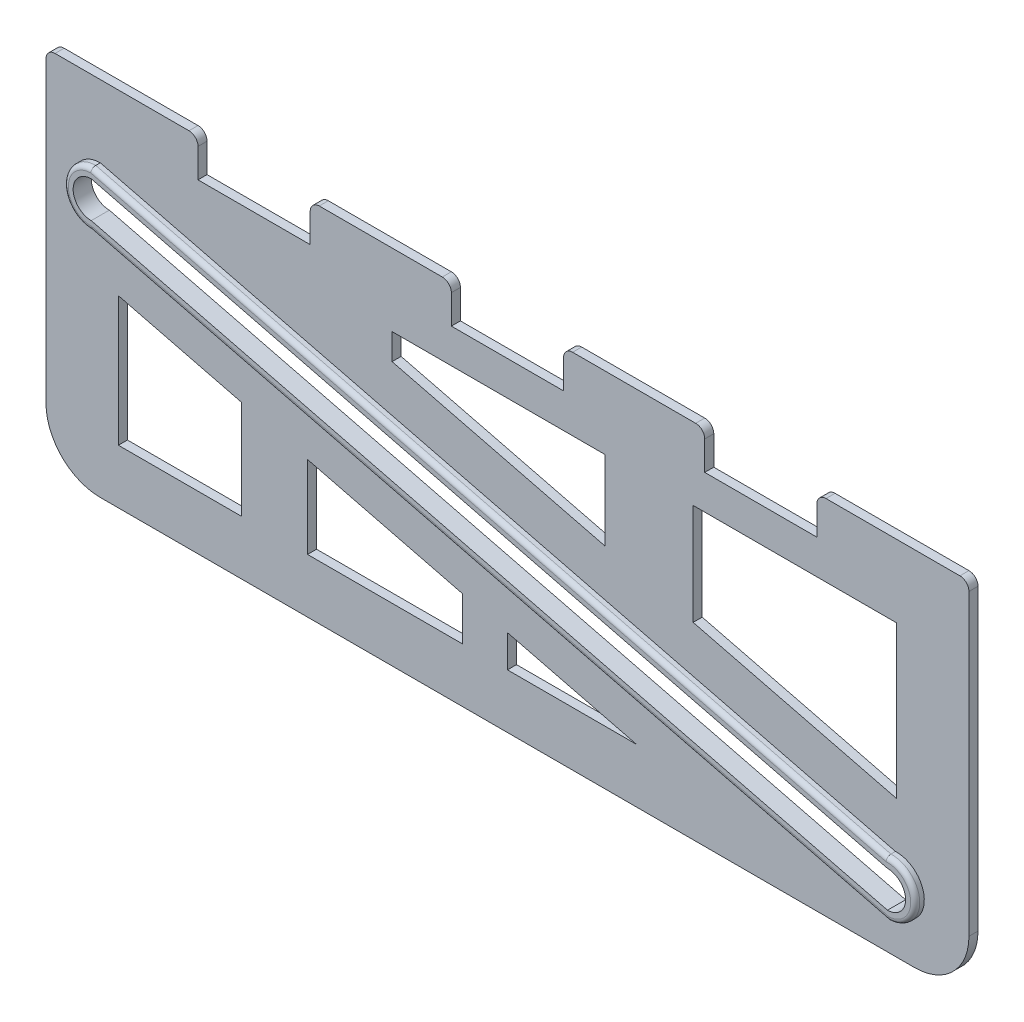
SolidWorks part; units mm, degrees
material "Nylon 101"
ref_plane "Ebene vorne" through (0, 0, 0) normal (0, 0, 1) x (1, 0, 0)
ref_plane "Ebene oben" through (0, 0, 0) normal (0, 1, 0) x (1, 0, 0)
ref_plane "Ebene rechts" through (0, 0, 0) normal (1, 0, 0) x (0, 0, -1)
sketch "jiggy" plane through (0, 0, 0) normal (0, 0, 1) x (1, 0, 0)
  line L0 (-44, 0) -> (44, 0) construction
  line L1 (-44, 11) -> (44, 11) construction
  line L2 (-44, -11) -> (44, -11) construction
  line L3 (-44, 11) -> (44, -11) construction
  line L4 (0, 36.5789) -> (0, -38.0526) construction
  line L5 (-44, 15) -> (44, 15) construction
  line L6 (44, 36.5789) -> (44, -33.902) construction
  line L7 (-44, 15) -> (44, -7) construction
  line L8 (-44, 15) -> (44, -7)
  line L9 (-44, 11) -> (44, -11)
  line L10 (-44, 11) -> (-44, -20.0087)
  line L12 (-50, 24) -> (52, 24)
  line L13 (-50, 24) -> (-50, -16)
  line L14 (-50, -16) -> (52, -16)
  line L15 (52, 24) -> (52, -16)
  arc A0 (-44, 15) -> (-44, 11) centre (-44, 13) ccw
  arc A1 (44, -7) -> (44, -11) centre (44, -9) cw
  point P13 (-44, 13)
  point P17 (44, -9)
  dimension "D10" = 2
  dimension "D11" = 8
  dimension "D1" = 11
  dimension "D2" = 11
  dimension "D3" = 44
  dimension "D4" = 44
  dimension "D5" = 44
  dimension "D6" = 44
  dimension "D7" = 4
  dimension "D8" = 3.8806
  dimension "D9" = 2
  dimension "D12" = 6
  dimension "D13" = 9
  dimension "D14" = 5
extrude "jig" add sketch "jiggy" along normal mid plane 1 contours L15 L12 L13 L14 L8 A1 L9 A0 region at (1.0981, 4.1962, 0)
sketch "border-sketch" plane through (0, 0, 0.5) normal (0, 0, 1) x (1, 0, 0)
  line L0 (-44, 15) -> (-44, 24) construction
  line L1 (-50, 24) -> (52, 24) construction
  line L2 (-44, 9.9692) -> (44.1213, -12.0611)
  line L4 (-44, 11) -> (44, -11)
  line L5 (-44, 15) -> (44, -7)
  line L6 (-44, 15) -> (44, -7) construction
  line L7 (-44, 16.0308) -> (43.8787, -5.9389)
  arc A0 (44, -11) -> (44, -7) centre (44, -9) ccw construction
  arc A1 (-44, 16.0308) -> (-44, 9.9692) centre (-44, 13) ccw
  arc A2 (43.8787, -5.9389) -> (44.1213, -12.0611) centre (44, -9) cw
  arc A3 (-44, 15) -> (-44, 11) centre (-44, 13) ccw
  arc A4 (44, -7) -> (44, -11) centre (44, -9) cw
  dimension "D1" = 1
  dimension "D2" = 1
extrude "border" add sketch "border-sketch" along normal blind 1
sketch "cut-scetch" plane through (0, 0, 0.5) normal (0, 0, 1) x (1, 0, 0)
  line L0 (-50, -10) -> (52, -10) construction
  line L1 (-50, 24) -> (-50, -16) construction
  line L2 (52, 24) -> (52, -16) construction
  line L3 (-42, 24) -> (-42, -16) construction
  line L4 (-50, 24) -> (52, 24) construction
  line L5 (-50, -16) -> (52, -16) construction
  line L6 (-42, 4.3153) -> (15.2614, -10) construction
  line L7 (-44, 11) -> (44, -11) construction
  line L8 (-42, 4.3153) -> (-42, -10)
  line L9 (-42, -10) -> (-28.3834, -10)
  line L10 (-28.3834, -10) -> (-28.3834, 0.9112)
  line L11 (-28.3834, 0.9112) -> (-42, 4.3153)
  line L12 (-21.0979, -0.9102) -> (-21.0979, -10)
  line L13 (-21.0979, -10) -> (-3.9806, -10)
  line L14 (-3.9806, -10) -> (-3.9806, -5.1895)
  line L15 (-3.9806, -5.1895) -> (-21.0979, -0.9102)
  line L16 (1, -6.4347) -> (1, -10)
  line L17 (1, -10) -> (15.2614, -10)
  line L18 (15.2614, -10) -> (1, -6.4347)
  line L19 (-50, 16) -> (52, 16) construction
  line L20 (44, -16) -> (44, 24) construction
  line L21 (44, -0.8153) -> (-23.2614, 16) construction
  line L22 (44, -7) -> (-44, 15) construction
  line L23 (21.5191, 16) -> (21.5191, 4.8049)
  line L24 (21.5191, 4.8049) -> (44, -0.8153)
  line L25 (44, -0.8153) -> (44, 16)
  line L26 (44, 16) -> (21.5191, 16)
  line L27 (11.7611, 16) -> (11.7611, 7.2444)
  line L28 (11.7611, 7.2444) -> (-11.7532, 13.123)
  line L29 (-11.7532, 13.123) -> (-11.7532, 16)
  line L30 (-11.7532, 16) -> (11.7611, 16)
  dimension "D1" = 8
  dimension "D2" = 6
  dimension "D3" = 8
  dimension "D4" = 8
  dimension "D5" = 6
  dimension "D6" = 6
extrude "cuts" cut sketch "cut-scetch" against normal through all both and the other way through all
fillet "Verrundung4" radius 6 2 edges at (52, -16, 0) (-50, -16, 0)
fillet "Verrundung5" radius 0.5 4 edges at (47.0611, -8.8787, 1.5) (0.0606, -1.0459, 1.5) (-47.0308, 13, 1.5) (-0.0606, 5.0459, 1.5)
sketch "fillet-" plane through (0, 0, 0.5) normal (0, 0, 1) x (1, 0, 0)
  line L0 (1, 24) -> (1, -16) construction
  line L1 (-50, 24) -> (52, 24) construction
  line L2 (-44, -16) -> (46, -16) construction
  line L3 (-50, 21.85) -> (52, 21.85) construction
  line L4 (-50, 24) -> (-50, -10) construction
  line L5 (52, 24) -> (52, -10) construction
  line L7 (-5.2, 19.8) -> (7.2, 19.8)
  line L8 (-5.2, 19.8) -> (-5.2, 24)
  line L9 (-5.2, 24) -> (7.2, 24)
  line L10 (7.2, 19.8) -> (7.2, 24)
  line L11 (-5.2, 19.8) -> (7.2, 24) construction
  line L12 (-5.2, 24) -> (7.2, 19.8) construction
  point P12 (1, 21.9)
  dimension "D1" = 2.15
  dimension "D2" = 12.4
extrude "fillet" cut sketch "fillet-" against normal through all
pattern_linear "Lineares Muster1" count 2 spacing 28 along (1, 0, 0) of "fillet"
pattern_linear "Lineares Muster2" count 2 spacing 28 along (-1, 0, 0) of "fillet"
fillet "Verrundung6" radius 1 6 edges at (-33.2, 24, 0) (35.2, 24, 0) (22.8, 24, 0) (7.2, 24, 0) (-5.2, 24, 0) (-20.8, 24, 0)
fillet "Verrundung7" radius 1 2 edges at (52, 24, 0) (-50, 24, 0)
